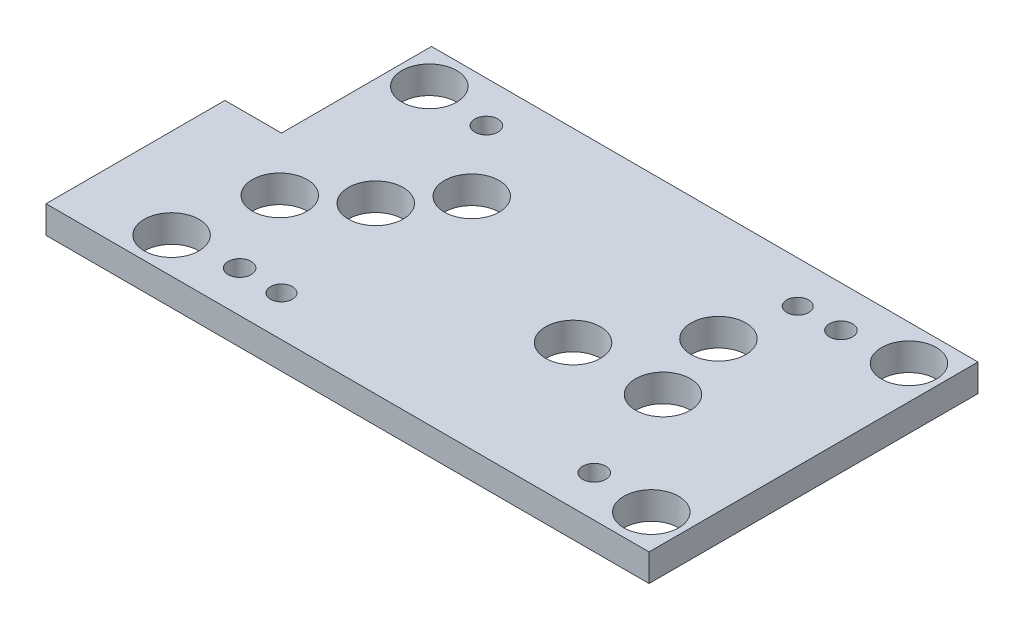
SolidWorks part; units mm, degrees
material "K110"
ref_plane "Front Plane" through (0, 0, 0) normal (0, 0, 1) x (1, 0, 0)
ref_plane "Top Plane" through (0, 0, 0) normal (0, 1, 0) x (1, 0, 0)
ref_plane "Right Plane" through (0, 0, 0) normal (1, 0, 0) x (0, 0, -1)
sketch "Sketch1" plane through (0, 0, 0) normal (0, 1, 0) x (1, 0, 0)
  line L1 (-110, -60) -> (110, -60)
  line L2 (-110, -60) -> (-110, 60)
  line L3 (-110, 60) -> (110, 60)
  line L4 (110, -60) -> (110, 60)
  line L5 (-110, -60) -> (110, 60) construction
  line L6 (-110, 60) -> (110, -60) construction
  point P0 (0, 0)
  dimension "D1" = 120
  dimension "D2" = 220
extrude "Boss-Extrude1" add sketch "Sketch1" against normal blind 10
sketch "Sketch2" plane through (0, 0, 0) normal (0, 1, 0) x (1, 0, 0)
  line L1 (-110, 60) -> (-89.3675, 60)
  line L2 (-110, 60) -> (-110, 5.27)
  line L3 (-110, 5.27) -> (-89.3675, 5.27)
  line L4 (-89.3675, 60) -> (-89.3675, 5.27)
  line L5 (-90, -14.72) -> (-89.3675, 5.27) construction
  line L10 (-70, 0.28) -> (-89.3675, 5.27) construction
  circle A0 centre (-70, 0.28) radius 3.1 construction
  circle A1 centre (-90, -14.72) radius 3.1 construction
  dimension "D1" = 20
extrude "Cut-Extrude1" cut sketch "Sketch2" against normal up to next
sketch "Sketch3" plane through (0, 0, 0) normal (0, 1, 0) x (1, 0, 0)
  circle A0 centre (97.8163, -47) radius 10 construction
  circle A1 centre (-77.1837, -47) radius 10 construction
  circle A2 centre (-70, -14.72) radius 10 construction
  circle A3 centre (-50, 0.28) radius 10 construction
  circle A4 centre (30, -7.72) radius 10 construction
  circle A5 centre (62.8163, -7.72) radius 10 construction
  circle A6 centre (55.3163, 20) radius 10 construction
  circle A7 centre (97.8163, 47) radius 10 construction
  circle A8 centre (-34.6837, 20) radius 10 construction
  circle A9 centre (-77.1837, 47) radius 10 construction
  circle A10 centre (97.8163, -47) radius 10
  circle A11 centre (-77.1837, -47) radius 10
  circle A12 centre (-70, -14.72) radius 10
  circle A13 centre (-50, 0.28) radius 10
  circle A14 centre (30, -7.72) radius 10
  circle A15 centre (62.8163, -7.72) radius 10
  circle A16 centre (55.3163, 20) radius 10
  circle A17 centre (97.8163, 47) radius 10
  circle A18 centre (-34.6837, 20) radius 10
  circle A19 centre (-77.1837, 47) radius 10
extrude "Cut-Extrude2" cut sketch "Sketch3" against normal up to next
hole_wizard "Ø8.0mm Dowel Hole1" positions "Sketch6" profile "Sketch5" hole size "Ø8.0" standard "ISO" end condition through all
sketch "Sketch6" plane through (0, 0, 0) normal (0, 1, 0) x (1, 0, 0)
  point P0 (-38.8675, -45.241)
  point P3 (59.5, 44.7284)
sketch "Sketch5" plane through (-38.8675, 0, 45.241) normal (1, 0, 0) x (0, 0, 1)
  line L0 (0, 0) -> (0, 10)
  line L1 (0, 10) -> (4, 10)
  line L2 (4, 10) -> (4, 0)
  line L5 (4, 0) -> (0, 0)
  line L11 (0, -6.35) -> (0, 107.95) construction
  dimension "Thru Hole Dia." = 8
  dimension "Thru Hole Depth" = 10
hole_wizard "M8 Clearance Hole1" positions "Sketch9" profile "Sketch8" hole size "M8" standard "ISO" end condition through all
sketch "Sketch9" plane through (0, 0, 0) normal (0, 1, 0) x (1, 0, 0)
  point P0 (-54.3675, 45)
  point P3 (75, 45)
  point P6 (75, -45)
  point P9 (-54.3675, -45)
sketch "Sketch8" plane through (-54.3675, 0, -45) normal (1, 0, 0) x (0, 0, 1)
  line L0 (0, 0) -> (0, 10)
  line L1 (0, 10) -> (4.2, 10)
  line L2 (4.2, 10) -> (4.2, 0)
  line L5 (4.2, 0) -> (0, 0)
  line L11 (0, -6.35) -> (0, 107.95) construction
  dimension "Thru Hole Dia." = 8.4
  dimension "Thru Hole Depth" = 10
